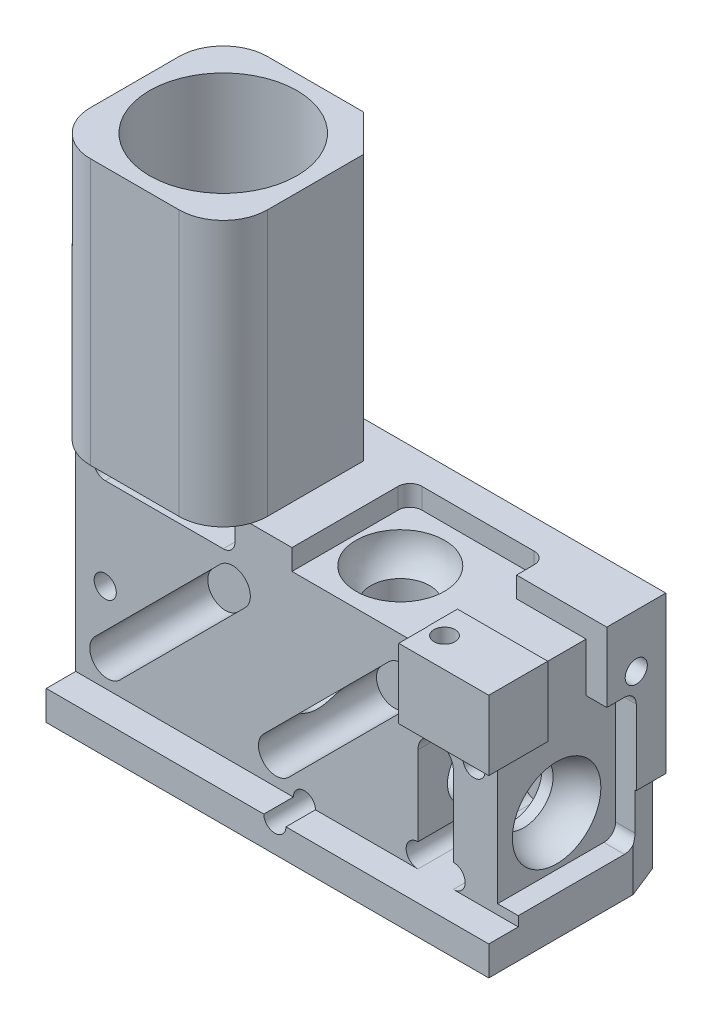
SolidWorks part; units mm, degrees
ref_plane "Front Plane" through (0, 0, 0) normal (0, 0, 1) x (1, 0, 0)
ref_plane "Top Plane" through (0, 0, 0) normal (0, 1, 0) x (1, 0, 0)
ref_plane "Right Plane" through (0, 0, 0) normal (1, 0, 0) x (0, 0, -1)
sketch "Sketch1" plane through (0, 0, 0) normal (0, 1, 0) x (1, 0, 0)
  line L1 (7.5, 3) -> (-7.5, 3)
  line L2 (7.5, 3) -> (7.5, -3)
  line L3 (7.5, -3) -> (-7.5, -3)
  line L4 (-7.5, 3) -> (-7.5, -3)
  line L5 (7.5, 3) -> (-7.5, -3) construction
  line L6 (7.5, -3) -> (-7.5, 3) construction
  point P0 (0, 0)
  dimension "D1" = 6
  dimension "D2" = 15
extrude "Main Body Ext" add sketch "Sketch1" along normal blind 8.3
sketch "Sketch8" plane through (0, 8.3, 0) normal (0, 1, 0) x (1, 0, 0)
  line L0 (-2.75, 3) -> (-1.5, 1.75)
  line L1 (-2.75, 3) -> (-7.5, 3)
  line L2 (-1.5, 1.75) -> (-1.5, -3)
  line L3 (-1.5, -3) -> (-7.5, -3)
  line L4 (-7.5, 3) -> (-7.5, -3)
  line L5 (-2.125, 2.375) -> (-7.5, -3) construction
  line L6 (-1.5, -3) -> (-7.5, 3) construction
  line L7 (-7.5, 3) -> (-7.5, -3) construction
  line L8 (0, 0) -> (-4.5, 0) construction
  point P0 (-4.5, 0)
  dimension "D1" = 6
  dimension "D2" = 6
  dimension "D3" = 1.25
  dimension "D4" = 3
extrude "Emission Path Ext" add sketch "Sketch8" along normal blind 9
sketch "Sketch3" plane through (0, 0, 0) normal (0, -1, 0) x (1, 0, 0)
  line L0 (-7.5, -3) -> (-7.5, 3) construction
  line L1 (0, 0) -> (-4.5, 0) construction
  circle A0 centre (-4.5, 0) radius 1.25
  dimension "D1" = 3
  dimension "D2" = 2.5
extrude "Emission and Grin Cut" cut sketch "Sketch3" against normal through all
sketch "Sketch4" plane through (7.5, 0, 0) normal (1, 0, 0) x (0, 0, -1)
  line L1 (-3, 0) -> (3, 0) construction
  circle A0 centre (0, 3) radius 1
  dimension "D1" = 2
  dimension "D2" = 3
extrude "Drum Lens Cut" cut sketch "Sketch4" against normal offset from surface (13 mm away) 2 up to face at (-7.5, 8.65, 0)
sketch "Sketch41" plane through (0, 8.3, 0) normal (0, 1, 0) x (1, 0, 0)
  line L1 (7.5, 3) -> (-2.75, 3) construction
  line L2 (-1.5, -3) -> (-1.5, 1.75) construction
  circle A0 centre (1.5, 0) radius 1
  dimension "D1" = 2
  dimension "D2" = 3
  dimension "D3" = 3
extrude "Addtl Light Source" cut sketch "Sketch41" against normal blind 5
sketch "Sketch5" plane through (0, 0, 3) normal (0, 0, 1) x (1, 0, 0)
  line L0 (-7.5, 0) -> (7.5, 0) construction
  line L1 (7.5, 8.3) -> (-7.5, 8.3)
  line L2 (7.5, 8.3) -> (7.5, 1)
  line L3 (7.5, 1) -> (-7.5, 1)
  line L4 (-7.5, 8.3) -> (-7.5, 1)
  line L5 (7.5, 8.3) -> (-7.5, 1) construction
  line L6 (7.5, 1) -> (-7.5, 8.3) construction
  line L7 (-1.5, 8.3) -> (7.5, 8.3) construction
  line L9 (7.5, 8.3) -> (7.5, 0) construction
  line L10 (-7.5, 17.3) -> (-7.5, 0) construction
  point P0 (0, 4.65)
  dimension "D1" = 1
extrude "FilterSet Cut1" cut sketch "Sketch5" against normal blind 1
sketch "Sketch6" plane through (0, 0, 2) normal (0, 0, 1) x (1, 0, 0)
  line L0 (5.3, 4.5) -> (5.3, 1.8)
  line L1 (4.1, 4.5) -> (5.3, 4.5) construction
  line L2 (5.3, 1) -> (4.1, 1)
  line L3 (-7.5, 1) -> (7.5, 1) construction
  line L4 (-7.5, 8.3) -> (-7.5, 1) construction
  line L5 (-6.9, 7.9) -> (-6.9, 7.5)
  line L6 (4.1, 4.5) -> (4.1, 1.8)
  line L7 (-1.5, 8.3) -> (-7.5, 8.3) construction
  line L8 (-2.1, 7.9) -> (-2.1, 7.5)
  line L9 (-6, 1.5) -> (-6, 1) construction
  line L10 (-2.5, 8.3) -> (-6.5, 8.3)
  line L11 (-4.5, 3) -> (-4.5, 1) construction
  line L12 (-4.5, 3) -> (0.4851, 3) construction
  line L13 (-2.5, 7.1) -> (-6.5, 7.1)
  line L14 (-0.282, 1.5) -> (-0.282, 1) construction
  line L15 (-2.5, 8.3) -> (-6.5, 7.1) construction
  line L16 (-2.5, 7.1) -> (-6.5, 8.3) construction
  line L17 (4.1, 1.8) -> (5.3, 1.8) construction
  line L18 (-2.6059, 6.5912) -> (-6.8485, 2.3485)
  line L19 (7.5, 1) -> (7.5, 8.3) construction
  line L20 (-1.7574, 5.7426) -> (-6, 1.5)
  line L21 (-2.6059, 6.5912) -> (-6, 1.5) construction
  line L22 (-6.8485, 2.3485) -> (-1.7574, 5.7426) construction
  line L23 (1.826, 3.6081) -> (1.826, 1.6081) construction
  line L24 (1.826, 3.6081) -> (3.2165, 3.6081) construction
  line L25 (3.1121, 6.5912) -> (-1.1305, 2.3485)
  line L26 (3.9606, 5.7426) -> (-0.282, 1.5)
  line L27 (3.1121, 6.5912) -> (-0.282, 1.5) construction
  line L28 (-1.1305, 2.3485) -> (3.9606, 5.7426) construction
  line L33 (-2.5, 8.3) -> (1.102, 8.3) construction
  line L34 (1.102, 8.3) -> (1.102, 7.1) construction
  line L35 (1.102, 7.1) -> (-2.5, 7.1) construction
  line L36 (-6.5, 7.1) -> (-4.098, 7.1) construction
  line L37 (-4.098, 7.1) -> (-4.098, 8.3) construction
  line L38 (-4.098, 8.3) -> (-6.5, 8.3) construction
  line L39 (-6.5, 8.3) -> (-2.7284, 6.992) construction
  arc A0 (-2.5, 8.3) -> (-2.1, 7.9) centre (-2.5, 7.9) cw
  arc A1 (4.1, 4.5) -> (5.3, 4.5) centre (4.7, 4.5) cw
  arc A2 (-6.5, 8.3) -> (-6.9, 7.9) centre (-6.5, 7.9) ccw
  arc A3 (-2.6059, 6.5912) -> (-1.7574, 5.7426) centre (-2.1816, 6.1669) cw
  arc A4 (4.1, 1) -> (4.1, 1.8) centre (4.1, 1.4) cw
  arc A5 (-6.8485, 2.3485) -> (-6, 1.5) centre (-6.4243, 1.9243) ccw
  arc A6 (5.3, 1) -> (5.3, 1.8) centre (5.3, 1.4) ccw
  arc A7 (-6.5, 7.1) -> (-6.9, 7.5) centre (-6.5, 7.5) cw
  arc A8 (-2.5, 7.1) -> (-2.1, 7.5) centre (-2.5, 7.5) ccw
  arc A9 (3.1121, 6.5912) -> (3.9606, 5.7426) centre (3.5364, 6.1669) cw
  arc A10 (-1.1305, 2.3485) -> (-0.282, 1.5) centre (-0.7063, 1.9243) ccw
  point P5 (-4.5, 7.7)
  point P10 (-4.3029, 4.0456)
  point P21 (1.415, 4.0456)
  dimension "D10" = 0.5
  dimension "D5" = 2.2
  dimension "D8" = 0.4
  dimension "D11" = 0.4
  dimension "D12" = 0.4
  dimension "D1" = 1.2
  dimension "D2" = 45
  dimension "D3" = 3.5
  dimension "D4" = 1.2
  dimension "D6" = 2
  dimension "D7" = 4
  dimension "D9" = 3
  dimension "D13" = 1.2
  dimension "D14" = 3
  dimension "D15" = 6
  dimension "D16" = 45
  dimension "D17" = 0.5
  dimension "D18" = 1.2
  dimension "D19" = 2
  dimension "D20" = 6
extrude "FilterSet Cut2" cut sketch "Sketch6" against normal offset from surface (4 mm away) 1 up to face at (-0.0625, 9.2833, -3)
sketch "Sketch10" plane through (0, 17.3, 0) normal (0, 1, 0) x (1, 0, 0)
  line L0 (-4.5, 0) -> (-4.5, -3) construction
  line L1 (-7.5, -3) -> (-1.5, -3) construction
  line L3 (-4.5, 0) -> (-7.5, 0) construction
  line L4 (-7.5, 3) -> (-7.5, -3) construction
  circle A0 centre (-4.5, 0) radius 2.5
  dimension "D1" = 5
extrude "Emission Lens Cut" cut sketch "Sketch10" against normal offset from surface (8.5 mm away) 0.5 up to face at (-4.125, 8.3, 1.3125)
sketch "Sketch12" plane through (7.5, 0, 0) normal (1, 0, 0) x (0, 0, -1)
  line L0 (0, 3.635) -> (0, 0) construction
  line L1 (1.6, 5.94) -> (-1.6, 5.94)
  line L2 (1.6, 5.94) -> (1.6, 1.33) construction
  line L3 (-2, 1.33) -> (1.6, 1.33)
  line L4 (-1.6, 5.94) -> (-1.6, 1.33) construction
  line L5 (1.6, 5.94) -> (-1.6, 1.33) construction
  line L6 (1.6, 1.33) -> (-1.6, 5.94) construction
  line L7 (-3, 0) -> (3, 0) construction
  line L9 (-1.6, 5.94) -> (-2, 5.94)
  line L10 (-2, 1) -> (-2, 8.3) construction
  line L11 (-2, 5.94) -> (-2, 1.33)
  line L12 (2, 5.54) -> (2, 1.73)
  arc A1 (1.6, 5.94) -> (2, 5.54) centre (1.6, 5.54) cw
  arc A2 (1.6, 1.33) -> (2, 1.73) centre (1.6, 1.73) ccw
  circle A3 centre (0, 3) radius 1 construction
  point P0 (0, 3.635)
  dimension "D2" = 4.61
  dimension "D3" = 1.67
  dimension "D1" = 3.2
  dimension "D4" = 0.4
sketch "Sketch15" plane through (0, 0, 0) normal (0, -1, 0) x (1, 0, 0)
  line L0 (-6.25, 1.875) -> (-6.25, -1.875) construction
  line L2 (2.5, 0) -> (-4.5, 0) construction
  line L3 (-4.5, 0) -> (-6.25, 0) construction
  circle A0 centre (-6.25, -1.875) radius 0.795
  circle A1 centre (-6.25, 1.875) radius 0.795
  circle A2 centre (2.5, 0) radius 0.795
  dimension "D4" = 1.59
  dimension "D1" = 3.75
  dimension "D2" = 7
  dimension "D3" = 1.75
extrude "Magnets Cut" cut sketch "Sketch15" against normal blind 0.9
sketch "Sketch18" plane through (0, 0, 2) normal (0, 0, 1) x (1, 0, 0)
  line L0 (-7.5, 8.3) -> (-7.5, 1) construction
  line L3 (-7.5, 0) -> (7.5, 0) construction
  line L4 (5.3, 1) -> (7.5, 1) construction
  line L7 (-7.5, 1) -> (4.1, 1) construction
  line L9 (-7.5, 1) -> (-7.5, 0) construction
  circle A0 centre (-6.5, 4) radius 0.375
  circle A1 centre (6, 5) radius 0.375
  circle A2 centre (0.25, 1) radius 0.375
  dimension "D1" = 0.75
  dimension "D2" = 1
  dimension "D3" = 4
  dimension "D4" = 13.5
  dimension "D5" = 3
  dimension "D6" = 1
  dimension "D7" = 7.75
extrude "Screw Holes Cut" cut sketch "Sketch18" against normal blind 3 and the other way through all
fillet "External Fillet 1" radius 1.5 2 edges at (-7.5, 8.65, -3)
sketch "Sketch14" plane through (0, 0, 0) normal (0, -1, 0) x (1, 0, 0)
  line L0 (7.5, -3) -> (7.5, -1.8916)
  line L1 (7.5, 3) -> (7.5, -3) construction
  line L2 (7.5, -1.8916) -> (7.0566, -3)
  line L3 (7.5, -3) -> (-6, -3) construction
  line L4 (7.0566, -3) -> (7.5, -3)
  line L5 (7.5, -3) -> (-7.5, 3) construction
  line L6 (-7.5, -1.5) -> (-7.5, 3) construction
  line L7 (-7.5, 3) -> (7.5, 3) construction
  dimension "D1" = 1.1938
sketch "Sketch28" plane through (0, 7.1, 0) normal (0, 1, 0) x (1, 0, 0)
  circle A0 centre (-4.5, 0) radius 1.5
  dimension "D1" = 3
extrude "Cut-Extrude8" cut sketch "Sketch28" against normal blind 4 and the other way through all
extrude "Cut-Extrude9" cut sketch "Sketch14" against normal blind 3
extrude "Cut-Extrude Original Light" cut sketch "Sketch12" against normal blind 0.7
sketch "Sketch44" plane through (0, 8.3, 0) normal (0, 1, 0) x (1, 0, 0)
  line L0 (-0.17, -2) -> (4.44, -2)
  line L1 (-0.17, -2) -> (-0.17, 1.6)
  line L2 (4.44, -2) -> (4.44, 1.6)
  line L3 (0.23, 2) -> (4.04, 2)
  line L6 (7.5, -2) -> (-1.5858, -2) construction
  circle A0 centre (1.5, 0) radius 1 construction
  arc A1 (4.44, 1.6) -> (4.04, 2) centre (4.04, 1.6) ccw
  arc A2 (-0.17, 1.6) -> (0.23, 2) centre (0.23, 1.6) cw
  point P10 (4.44, 2)
  point P13 (-0.17, 2)
  dimension "D3" = 1.67
  dimension "D4" = 0.4
  dimension "D5" = 0.4
  dimension "D1" = 4
  dimension "D2" = 4.61
extrude "Cut-Extrude Addtl Light" cut sketch "Sketch44" against normal blind 0.7
sketch "Sketch29" plane through (7.5, 0, 0) normal (1, 0, 0) x (0, 0, -1)
  line L0 (3, 8.3) -> (3, 3) construction
  line L1 (-2, 8.3) -> (3, 8.3) construction
  circle A0 centre (2, 6.5) radius 0.375
  dimension "D1" = 0.75
  dimension "D2" = 1
  dimension "D3" = 1.8
extrude "Cut-Extrude11" cut sketch "Sketch29" against normal blind 2.5
sketch "Sketch31" plane through (6.8, 0, 0) normal (1, 0, 0) x (0, 0, -1)
  circle A0 centre (0, 3) radius 1.6
  dimension "D1" = 3.2
sketch "Sketch32" plane through (7.5, 0, 0) normal (1, 0, 0) x (0, 0, -1)
  line L0 (-2, 8.3) -> (3, 8.3) construction
  line L1 (-1, 8.3) -> (1, 8.3)
  line L2 (-1, 8.3) -> (-1, 5.94)
  line L3 (-1, 5.94) -> (1, 5.94)
  line L4 (1, 8.3) -> (1, 5.94)
  line L5 (1.6, 5.94) -> (-2, 5.94) construction
  line L6 (-2, 5.94) -> (-2, 8.3) construction
  line L8 (3, 8.3) -> (3, 3) construction
  dimension "D1" = 1
  dimension "D2" = 2
extrude "Cut-Extrude14" cut sketch "Sketch32" against normal up to surface (0.7 mm away) up to face at (6.8, 3.635, -0.5609)
sketch "Sketch45" plane through (0, 8.3, 0) normal (0, 1, 0) x (1, 0, 0)
  line L1 (4.44, -1) -> (6.8, -1)
  line L2 (4.44, -1) -> (4.44, 1)
  line L3 (4.44, 1) -> (6.8, 1)
  line L4 (6.8, -1) -> (6.8, 1)
  line L5 (4.44, -1) -> (6.8, 1) construction
  line L6 (4.44, 1) -> (6.8, -1) construction
  line L7 (6.8, 1) -> (6.8, -1) construction
  line L8 (4.44, -2) -> (4.44, 1.6) construction
  line L12 (6.8, -1) -> (7.5, -1) construction
  line L13 (6.8, 1) -> (7.5, 1) construction
extrude "Cut-Extrude19" cut sketch "Sketch45" against normal blind 0.7
sketch "Sketch33" plane through (0, 0, 0) normal (0, 0, 1) x (1, 0, 0)
  line L0 (6.8, 3) -> (5.3, 3)
  line L1 (6.8, 1.4) -> (6.8, 4.6) construction
  line L2 (6.8, 3) -> (6.8, 4.5)
  arc A0 (5.3, 3) -> (6.8, 4.5) centre (6.8, 3) cw
  dimension "D2" = 1.5
revolve "Cut-Revolve1" cut sketch "Sketch33" angle 360 about L0
sketch "Sketch46" plane through (0, 7.6, 0) normal (0, 1, 0) x (1, 0, 0)
  circle A0 centre (1.5, 0) radius 1.5 construction
ref_plane "Plane1" through (1.5, 0, 0) normal (1, 0, 0) x (0, 0, -1)
sketch "Sketch47" plane through (1.5, 0, 0) normal (1, 0, 0) x (0, 0, -1)
  line L4 (-1.5, 7.6) -> (0, 7.6)
  line L5 (0, 7.6) -> (0, 6.1373)
  line L6 (1, 7.6) -> (-1, 7.6) construction
  arc A0 (0, 6.1373) -> (-1.5, 7.6) centre (0, 7.6378) cw
revolve "Cut-Revolve2" cut sketch "Sketch47" angle 360 about L5
sketch "Sketch36" plane through (0, 17.3, 0) normal (0, 1, 0) x (1, 0, 0)
  line L0 (-7.5, -1.5) -> (-7.5, -3)
  line L1 (-7.5, 1.5) -> (-7.5, -3) construction
  line L2 (-7.5, -3) -> (-6, -3)
  line L3 (-7.5, -3) -> (-3, -3) construction
  arc A0 (-7.5, -1.5) -> (-6, -3) centre (-6, -1.5) ccw
  dimension "D1" = 1.5
  dimension "D2" = 1.5
extrude "Cut-Extrude16" cut sketch "Sketch36" against normal up to surface (9 mm away) up to face at (-4.3971, 8.3, 1.2781)
sketch "Sketch37" plane through (0, 8.8, 0) normal (0, 1, 0) x (1, 0, 0)
  circle A0 centre (-4.5, 0) radius 2
  circle A1 centre (-4.5, 0) radius 1.5 construction
  dimension "D1" = 4
extrude "Cut-Extrude17" cut sketch "Sketch37" against normal up to next
sketch "Sketch49" plane through (0, 0, 2) normal (0, 0, 1) x (1, 0, 0)
  line L0 (6.8, 5.94) -> (7.5, 5.94) construction
  line L1 (7.5, 8.3) -> (4.4484, 8.3)
  line L2 (7.5, 8.3) -> (7.5, 5.94)
  line L3 (7.5, 5.94) -> (4.4484, 5.94)
  line L4 (4.4484, 8.3) -> (4.4484, 5.94)
  line L5 (7.0259, 5.94) -> (7.0264, 5.94)
  line L7 (7.0259, 5.9687) -> (7.0264, 5.9687)
  line L8 (7.0264, 5.94) -> (7.0264, 5.9687)
  point P9 (0, 0)
  dimension "D1" = 3.0516
extrude "Boss-Extrude2" add sketch "Sketch49" along normal blind 1 contours L4 L3 region at (5.9742, 7.12, 2)
sketch "Sketch51" plane through (0, 8.3, 0) normal (0, 1, 0) x (1, 0, 0)
  circle A0 centre (5, -2) radius 0.3567
  circle A1 centre (1.5, 0) radius 1 construction
  dimension "D1" = 2
  dimension "D2" = 3.5
extrude "Add'l Screw Hole" cut sketch "Sketch51" against normal blind 2
